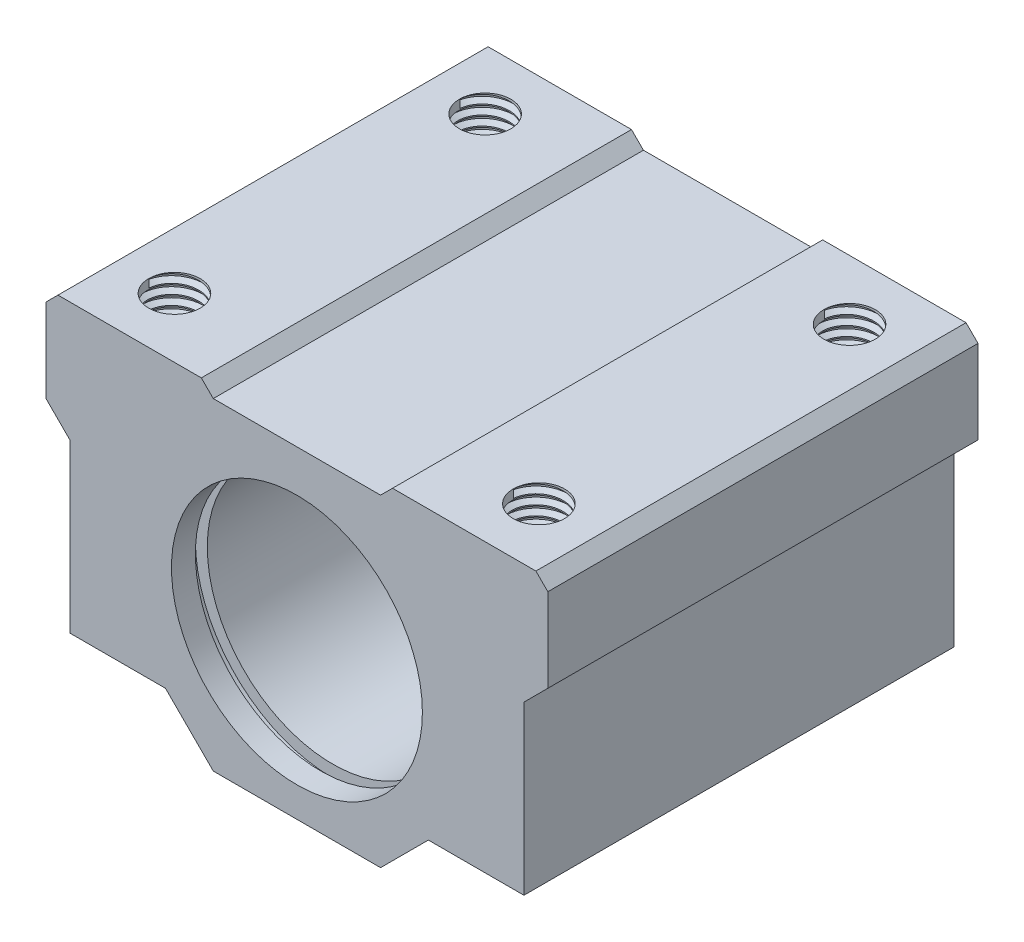
SolidWorks part; units mm, degrees
ref_plane "Front Plane" through (0, 0, 0) normal (0, 0, 1) x (1, 0, 0)
ref_plane "Top Plane" through (0, 0, 0) normal (0, 1, 0) x (1, 0, 0)
ref_plane "Right Plane" through (0, 0, 0) normal (1, 0, 0) x (0, 0, -1)
sketch "Sketch1" plane through (0, 0, 0) normal (0, 0, 1) x (1, 0, 0)
  line L0 (0, 0) -> (0, 16.8561) construction
  line L1 (-21, 14) -> (-20, 15)
  line L2 (-21, 14) -> (-21, 7)
  line L3 (-21, 7) -> (-19, 5)
  line L4 (-19, 5) -> (-19, -9)
  line L5 (-19, -9) -> (-11, -9)
  line L6 (-11, -9) -> (-7, -13)
  line L7 (-7, -13) -> (2.4386, -13)
  line L8 (-20, 15) -> (-8, 15)
  line L9 (-8, 15) -> (-7, 14)
  line L10 (-7, 14) -> (7, 14)
  line L11 (7, -13) -> (-2.4386, -13)
  line L12 (11, -9) -> (7, -13)
  line L13 (19, -9) -> (11, -9)
  line L14 (19, 5) -> (19, -9)
  line L15 (21, 7) -> (19, 5)
  line L16 (21, 14) -> (21, 7)
  line L17 (21, 14) -> (20, 15)
  line L18 (20, 15) -> (8, 15)
  line L19 (8, 15) -> (7, 14)
  circle A0 centre (0, 0) radius 10.5
  point P29 (0, 14)
  dimension "D1" = 21
  dimension "D2" = 135
  dimension "D3" = 135
  dimension "D4" = 1
  dimension "D5" = 8
  dimension "D6" = 2
  dimension "D7" = 15
  dimension "D8" = 28
  dimension "D9" = 135
  dimension "D10" = 24
  dimension "D11" = 8
  dimension "D12" = 12
  dimension "E" = 21
extrude "Boss-Extrude1" add sketch "Sketch1" along normal blind 36 contours A0 L10 L9 L8 L1 L2 L3 L4 L5 L6 L7 L11 L12 L13 L14 L15 L16 L17 L18 L19 region at (-20.1431, 14.1431, 0)
ref_plane "Plane1" through (0, 0, 3) normal (0, 0, -1) x (-1, 0, 0)
sketch "Sketch2" plane through (0, 0, 3) normal (0, 0, -1) x (-1, 0, 0)
  circle A0 centre (0, 0) radius 11.5
  circle A1 centre (0, 0) radius 10.5 construction
  dimension "D1" = 1
extrude "Cut-Extrude1" cut sketch "Sketch2" along normal blind 1
ref_plane "Plane2" through (0, 0, 33) normal (0, 0, 1) x (1, 0, 0)
sketch "Sketch3" plane through (0, 0, 33) normal (0, 0, 1) x (1, 0, 0)
  circle A0 centre (0, 0) radius 11.5
  circle A1 centre (0, 0) radius 10.5 construction
  dimension "D1" = 1
extrude "Cut-Extrude2" cut sketch "Sketch3" along normal blind 1
sketch "Sketch4" plane through (0, 15, 0) normal (0, 1, 0) x (1, 0, 0)
  line L0 (15.25, -36) -> (15.25, 0) construction
  line L1 (20, -36) -> (8, -36) construction
  line L2 (20, 0) -> (8, 0) construction
  line L3 (-15.25, 0) -> (-15.25, -36) construction
  line L4 (-20, 0) -> (-8, 0) construction
  line L5 (-20, -36) -> (-8, -36) construction
  line L6 (21, -36) -> (21, 0) construction
  line L7 (-21, -36) -> (-21, 0) construction
  circle A0 centre (15.25, -31) radius 2.15
  circle A1 centre (15.25, -5) radius 2.15
  circle A2 centre (-15.25, -5) radius 2.15
  circle A3 centre (-15.25, -31) radius 2.15
  dimension "D9" = 4.3
  dimension "D10" = 4.3
  dimension "D11" = 4.3
  dimension "D12" = 4.3
  dimension "D1" = 26
  dimension "D2" = 26
  dimension "D3" = 5
  dimension "D4" = 5
  dimension "D5" = 5
  dimension "D6" = 5
  dimension "D7" = 5.75
  dimension "D8" = 5.75
extrude "Cut-Extrude3" cut sketch "Sketch4" against normal through all
sketch "Sketch5" plane through (0, 15, 0) normal (0, 1, 0) x (1, 0, 0)
  circle A0 centre (15.25, -5) radius 2.5
  circle A1 centre (15.25, -31) radius 2.5
  circle A2 centre (-15.25, -31) radius 2.5
  circle A3 centre (-15.25, -5) radius 2.5
  dimension "D1" = 5
  dimension "D2" = 5
  dimension "D3" = 5
  dimension "D4" = 5
extrude "Cut-Extrude4" [suppressed] cut sketch "Sketch5" against normal blind 12
chamfer "Chamfer1" [suppressed] distance 1 angle 45
chamfer "Chamfer2" distance 0.75 angle 45 4 edges at (15.25, -9, 2.85) (-15.25, -9, 7.15) (-15.25, -9, 33.15) (15.25, -9, 28.85)
thread "Thread1" pitch 0.8 method cut profile "Thread Profile1" start angle 1, offset 0, length 12, pitch 0.8, diameter 4.3
ref_plane "Plane3" through (-17.3997, 15, 4.9625) normal (-0.0175, 0, 0.9998) x (-0.9998, 0, -0.0175)
sketch "Thread Profile1" plane through (-17.3997, 15, 4.9625) normal (-0.0175, 0, 0.9998) x (-0.9998, 0, -0.0175)
  line L0 (0, 0) -> (0, 0.8) construction
  line L11 (0, 0.7) -> (0, 0)
  line L12 (0, 0) -> (0.433, 0.25)
  line L13 (0.433, 0.25) -> (0.433, 0.45)
  line L15 (0.433, 0.45) -> (0, 0.7)
  line L17 (0.433, 0.35) -> (0, 0.35) construction
  point P3 (0, 0)
  dimension "Pitch" = 0.8
  dimension "Profile_Angle" = 60
  dimension "Profile_Land" = 0.2
  dimension "Profile_Height" = 0.433
thread "Thread2" pitch 0.8 method cut profile "Thread Profile2" start angle 1, offset 0, length 12, pitch 0.8, diameter 4.3
ref_plane "Plane4" through (13.1003, 15, 4.9625) normal (-0.0175, 0, 0.9998) x (-0.9998, 0, -0.0175)
sketch "Thread Profile2" plane through (13.1003, 15, 4.9625) normal (-0.0175, 0, 0.9998) x (-0.9998, 0, -0.0175)
  line L0 (0, 0) -> (0, 0.8) construction
  line L11 (0, 0.7) -> (0, 0)
  line L12 (0, 0) -> (0.433, 0.25)
  line L13 (0.433, 0.25) -> (0.433, 0.45)
  line L15 (0.433, 0.45) -> (0, 0.7)
  line L17 (0.433, 0.35) -> (0, 0.35) construction
  point P3 (0, 0)
  dimension "Pitch" = 0.8
  dimension "Profile_Angle" = 60
  dimension "Profile_Land" = 0.2
  dimension "Profile_Height" = 0.433
thread "Thread3" pitch 0.8 method cut profile "Thread Profile3" start angle 1, offset 0, length 12, pitch 0.8, diameter 4.3
ref_plane "Plane5" through (13.1003, 15, 30.9625) normal (-0.0175, 0, 0.9998) x (-0.9998, 0, -0.0175)
sketch "Thread Profile3" plane through (13.1003, 15, 30.9625) normal (-0.0175, 0, 0.9998) x (-0.9998, 0, -0.0175)
  line L0 (0, 0) -> (0, 0.8) construction
  line L11 (0, 0.7) -> (0, 0)
  line L12 (0, 0) -> (0.433, 0.25)
  line L13 (0.433, 0.25) -> (0.433, 0.45)
  line L15 (0.433, 0.45) -> (0, 0.7)
  line L17 (0.433, 0.35) -> (0, 0.35) construction
  point P3 (0, 0)
  dimension "Pitch" = 0.8
  dimension "Profile_Angle" = 60
  dimension "Profile_Land" = 0.2
  dimension "Profile_Height" = 0.433
thread "Thread4" pitch 0.8 method cut profile "Thread Profile4" start angle 1, offset 0, length 12, pitch 0.8, diameter 4.3
ref_plane "Plane6" through (-17.3997, 15, 30.9625) normal (-0.0175, 0, 0.9998) x (-0.9998, 0, -0.0175)
sketch "Thread Profile4" plane through (-17.3997, 15, 30.9625) normal (-0.0175, 0, 0.9998) x (-0.9998, 0, -0.0175)
  line L0 (0, 0) -> (0, 0.8) construction
  line L11 (0, 0.7) -> (0, 0)
  line L12 (0, 0) -> (0.433, 0.25)
  line L13 (0.433, 0.25) -> (0.433, 0.45)
  line L15 (0.433, 0.45) -> (0, 0.7)
  line L17 (0.433, 0.35) -> (0, 0.35) construction
  point P3 (0, 0)
  dimension "Pitch" = 0.8
  dimension "Profile_Angle" = 60
  dimension "Profile_Land" = 0.2
  dimension "Profile_Height" = 0.433
